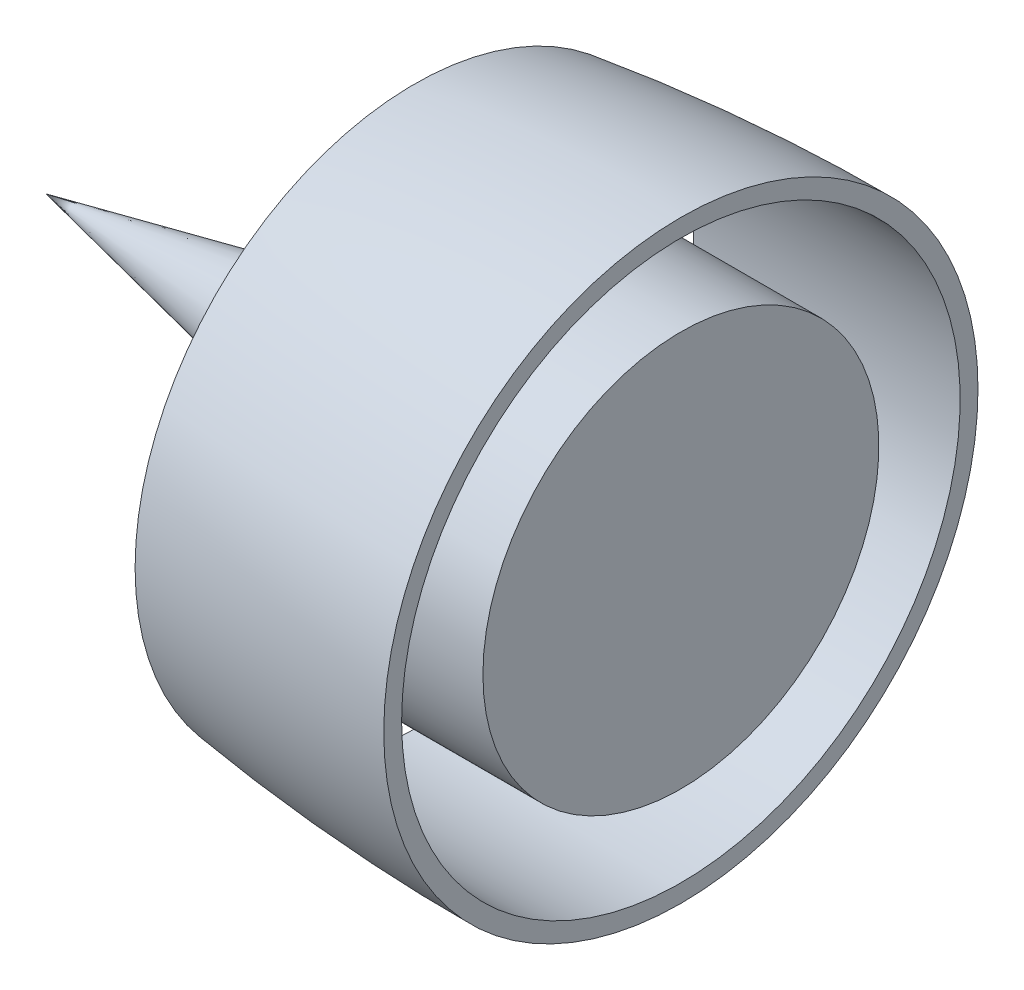
SolidWorks part; units mm, degrees
ref_plane "Piano frontale" through (0, 0, 0) normal (0, 0, 1) x (1, 0, 0)
ref_plane "Piano superiore" through (0, 0, 0) normal (0, 1, 0) x (1, 0, 0)
ref_plane "Piano destro" through (0, 0, 0) normal (1, 0, 0) x (0, 0, -1)
sketch "Schizzo1" plane through (0, 0, 0) normal (0, 0, 1) x (1, 0, 0)
  line L0 (0, 0) -> (248.8482, 51.9871)
  line L1 (248.8482, 51.9871) -> (402.7039, 127.6935)
  line L2 (402.7039, 127.6935) -> (495.4093, 216.9059)
  line L3 (0, 0) -> (248.8482, 51.9871)
  line L4 (0, 0) -> (495.4093, 0)
  line L5 (495.4093, 0) -> (495.4093, 216.9059) construction
  line L6 (0, 0) -> (402.8987, 313.0387) construction
  line L7 (402.8987, 313.0387) -> (248.8482, 51.9871) construction
  line L8 (495.4093, 216.9059) -> (402.8987, 313.0387) construction
  line L9 (402.8987, 313.0387) -> (402.7039, 127.6935) construction
  line L10 (495.4093, 216.9059) -> (500.6012, 221.9022)
  line L11 (402.8987, 313.0387) -> (412.8987, 313.0387) construction
  line L12 (412.8987, 313.0387) -> (500.6012, 221.9022) construction
  line L13 (500.6012, 221.9022) -> (711.6209, 221.9022)
  line L14 (711.6209, 221.9022) -> (711.6209, 0)
  line L15 (711.6209, 0) -> (495.4093, 0)
  line L16 (412.8987, 313.0387) -> (711.6209, 313.0387)
  line L17 (208.5777, 333.0387) -> (50208.5777, 333.0387) construction
  line L19 (711.6209, 333.0387) -> (711.6209, 313.0387)
  line L20 (-275.0185, 0) -> (49724.9815, 0) construction
  arc A0 (412.8987, 313.0387) -> (711.6209, 333.0387) centre (711.6209, -1907.8359) cw
  dimension "D1" = 11.8
  dimension "D2" = 26.2
  dimension "D3" = 43.9
  dimension "D4" = 26.046
  dimension "D5" = 33.255
  dimension "D6" = 46.04
  dimension "D7" = 126.4816
  dimension "D8" = 10
  dimension "D9" = 20
  dimension "D10" = 216.2116
revolve "Rivoluzione1" add sketch "Schizzo1" angle 360 about L20 region at (497.5859, 89.0063, 0) region at (599.5331, 321.0417, 0)
